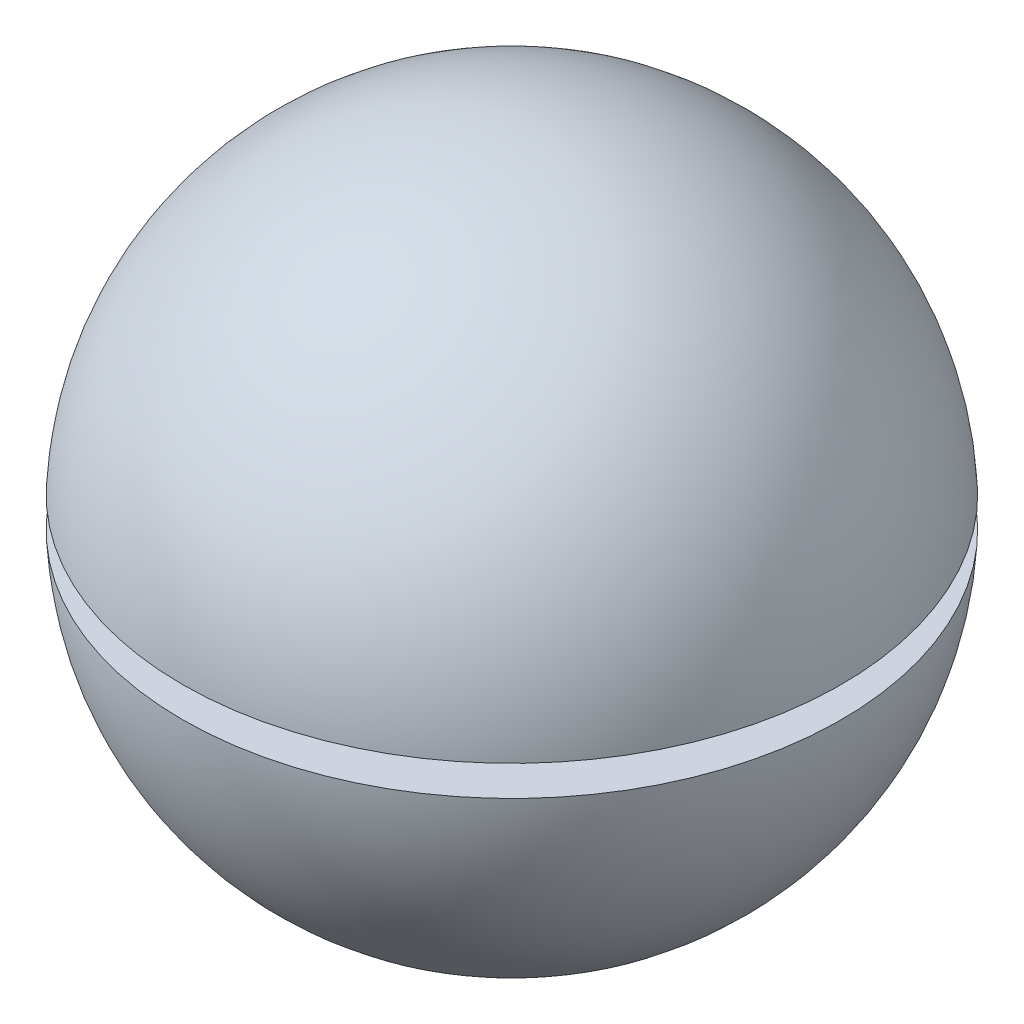
SolidWorks part; units mm, degrees
ref_plane "Front Plane" through (0, 0, 0) normal (0, 0, 1) x (1, 0, 0)
ref_plane "Top Plane" through (0, 0, 0) normal (0, 1, 0) x (1, 0, 0)
ref_plane "Right Plane" through (0, 0, 0) normal (1, 0, 0) x (0, 0, -1)
sketch "Sketch1" plane through (0, 0, 0) normal (0, 0, 1) x (1, 0, 0)
  line L0 (-44.45, 0) -> (44.45, 0)
  arc A0 (44.45, 0) -> (-44.45, 0) centre (0, 0) ccw
  dimension "D1" = 88.9
revolve "Revolve1" add sketch "Sketch1" angle 360 about L0
sketch "Sketch2" plane through (0, 0, 0) normal (0, 0, 1) x (1, 0, 0)
  line L0 (-1000, 0) -> (49000, 0) construction
  line L1 (0, -1000) -> (0, 49000) construction
  line L2 (0, 0) -> (-38.4948, 22.225)
  line L3 (0, 0) -> (-38.4948, -22.225)
  line L4 (0, 0) -> (-42.9354, 11.5045)
  line L5 (0, 0) -> (-41.0664, 17.0103)
  circle A0 centre (0, 0) radius 44.45 construction
  dimension "D1" = 30
  dimension "D2" = 15
  dimension "D3" = 7.5
sketch "Sketch3" plane through (0, 0, 0) normal (0, 1, 0) x (1, 0, 0)
  circle A0 centre (0, 0) radius 78.4125
extrude "Cut-Extrude1" cut sketch "Sketch3" against normal mid plane 4.1
